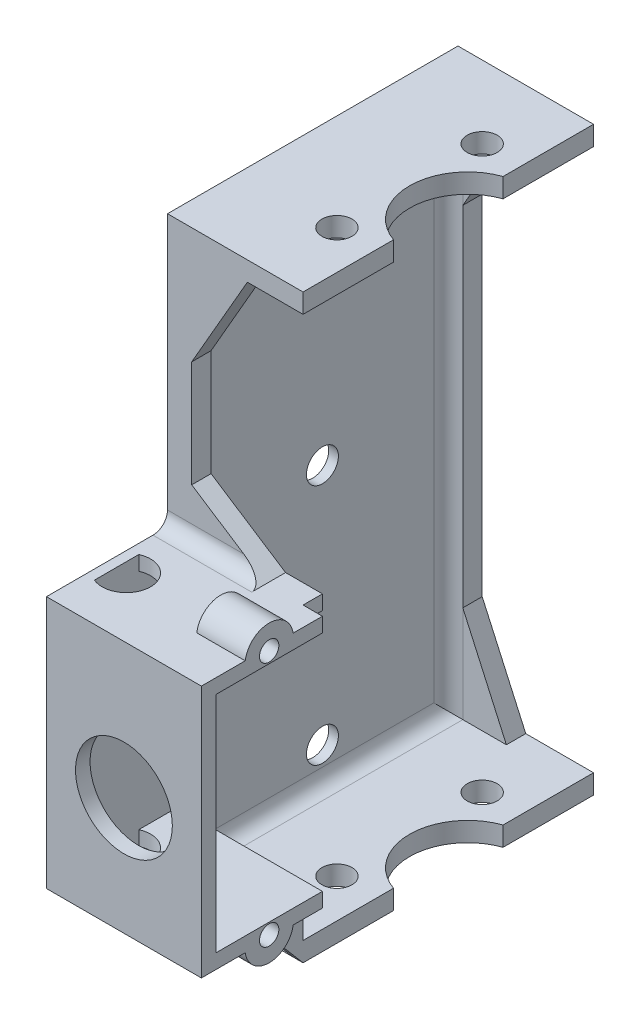
SolidWorks part; units mm, degrees
ref_plane "Alzado" through (0, 0, 0) normal (0, 0, 1) x (1, 0, 0)
ref_plane "Planta" through (0, 0, 0) normal (0, 1, 0) x (1, 0, 0)
ref_plane "Vista lateral" through (0, 0, 0) normal (1, 0, 0) x (0, 0, -1)
sketch "Croquis1" plane through (0, 0, 0) normal (1, 0, 0) x (0, 0, -1)
  line L0 (0, 12.5) -> (0, -12.5) construction
  line L1 (-15, 18) -> (15, 18) construction
  line L2 (-15, 18) -> (-15, -18)
  line L3 (-15, -18) -> (15, -18)
  line L4 (15, 18) -> (15, -18)
  line L5 (-15, 18) -> (15, -18) construction
  line L6 (-15, -18) -> (15, 18) construction
  line L9 (-15, 18) -> (-15, 42)
  line L10 (-15, 42) -> (15, 42)
  line L11 (15, 18) -> (15, 42)
  circle A0 centre (0, 12.5) radius 1.65
  circle A1 centre (0, -12.5) radius 1.65
  point P0 (0, 0)
  point P10 (0, 0)
  dimension "D3" = 25
  dimension "D4" = 3.3
  dimension "D1" = 30
  dimension "D2" = 36
  dimension "D5" = 24
extrude "Saliente-Extruir1" add sketch "Croquis1" along normal blind 1
sketch "screwHeadClearance" plane through (1, 0, 0) normal (1, 0, 0) x (0, 0, -1)
  circle A0 centre (0, 12.5) radius 3.175 construction
  circle A1 centre (0, -12.5) radius 3.175 construction
  point P6 (0, 0)
  point P7 (0, 0)
  dimension "D1" = 6.35
sketch "Croquis3" plane through (1, 0, 0) normal (1, 0, 0) x (0, 0, -1)
  line L0 (15, -18) -> (15, 42) construction
  line L1 (-15, 42) -> (15, 42)
  line L2 (-15, 42) -> (-15, 40)
  line L3 (-15, 40) -> (15, 40)
  line L4 (15, 42) -> (15, 40)
  line L6 (-15, -18) -> (15, -18)
  line L7 (-15, -18) -> (-15, -16)
  line L8 (-15, -16) -> (15, -16)
  line L9 (15, -18) -> (15, -16)
  point P12 (0, 0)
  dimension "D1" = 2
  dimension "D2" = 2
extrude "Saliente-Extruir2" add sketch "Croquis3" along normal blind 13
sketch "Croquis4" plane through (0, 42, 0) normal (0, 1, 0) x (1, 0, 0)
  line L0 (10, 7.5) -> (10, -7.5) construction
  line L1 (14, 15) -> (14, -15) construction
  line L2 (14, 5.6569) -> (14, -5.6569)
  circle A0 centre (10, 7.5) radius 1.55
  circle A1 centre (10, -7.5) radius 1.55
  arc A2 (14, -5.6569) -> (14, 5.6569) centre (16, 0) cw
  point P4 (10, 0)
  dimension "D2" = 3.1
  dimension "D4" = 6
  dimension "D1" = 15
  dimension "D3" = 4
  dimension "D5" = 2
extrude "Cortar-Extruir1" cut sketch "Croquis4" against normal through all
sketch "Croquis8" plane through (0, 0, 0) normal (1, 0, 0) x (0, 0, -1)
  line L0 (-15, 40) -> (-15, -16) construction
  line L1 (-26, 12.5) -> (-15, 12.5)
  line L2 (-26, 12.5) -> (-26, -10.608)
  line L3 (-26, -10.608) -> (-15, -10.608)
  line L4 (-15, 12.5) -> (-15, -10.608)
  point P6 (-20.5, 12.5)
  dimension "D1" = 11
  dimension "D2" = 23.108
extrude "Saliente-Extruir4" add sketch "Croquis8" along normal up to surface (1 mm away) up to face at (1, 12.5, -1.65)
sketch "Croquis9" plane through (0, 0, 0) normal (1, 0, 0) x (0, 0, -1)
  line L0 (-15, -10.608) -> (-15, -16) construction
  line L1 (-26, 12.5) -> (-15, 12.5)
  line L2 (-26, 12.5) -> (-26, -10.608)
  line L3 (-26, -10.608) -> (-15, -10.608)
  line L4 (-15, 12.5) -> (-15, -10.608)
  line L5 (-27.5, 14) -> (-15, 14)
  line L6 (-27.5, 14) -> (-27.5, -12.108)
  line L7 (-27.5, -12.108) -> (-15, -12.108)
  line L8 (-15, 14) -> (-15, -12.108)
  point P12 (-20.5, -10.608)
  dimension "D1" = 1.5
  dimension "D2" = 1.5
  dimension "D3" = 1.5
extrude "Saliente-Extruir5" add sketch "Croquis9" along normal blind 16 contours L8 L5 L6 L7 L3 L2 L1 region at (0, 0.946, 26.2895)
sketch "Croquis10" plane through (0, 14, 0) normal (0, 1, 0) x (1, 0, 0)
  line L0 (0, -27.5) -> (0, -15) construction
  line L1 (1, -18.9587) -> (1, -23.5413)
  circle A0 centre (2, -21.25) radius 2.5
  point P5 (0, -21.25)
  dimension "D2" = 5
  dimension "D1" = 2
  dimension "D3" = 1
extrude "Cortar-Extruir2" cut sketch "Croquis10" against normal through all contours L1 A0 region at (2.5463, 14, 21.25)
sketch "Croquis11" plane through (16, 0, 0) normal (1, 0, 0) x (0, 0, -1)
  line L0 (-26, 12.5) -> (-15, 12.5) construction
  line L1 (-20.5, 13.646) -> (-20.5, -11.754) construction
  line L2 (-26, 12.5) -> (-26, -10.608) construction
  line L3 (-22.7219, 12.5) -> (-18.2781, 12.5)
  line L4 (-15, 12.5) -> (-18.9587, 12.5) construction
  line L5 (-22.7219, -10.608) -> (-18.2781, -10.608)
  line L6 (-26, -10.608) -> (-15, -10.608) construction
  circle A0 centre (-20.5, 13.646) radius 1
  circle A1 centre (-20.5, 13.646) radius 2.5
  circle A2 centre (-20.5, -11.754) radius 1
  circle A3 centre (-20.5, -11.754) radius 2.5
  point P5 (-20.5, 12.5)
  point P8 (-20.5, 0.946)
  point P11 (-26, 0.946)
  line M2 (-15, 14) -> (-27.5, 14)
  line M4 (-27.5, -12.108) -> (-15, -12.108)
  dimension "D1" = 5
  dimension "D2" = 25.4
  dimension "D3" = 2
  dimension "D4" = 5
extrude "Saliente-Extruir6" add sketch "Croquis11" against normal blind 5 contours A3 A2 M4 | A1 A0 M2 region at (16, 14.9782, 20.5) region at (16, -13.0862, 20.5)
sketch "Croquis12" plane through (16, 0, 0) normal (1, 0, 0) x (0, 0, -1)
  circle A0 centre (-20.5, -11.754) radius 1
  circle A1 centre (-20.5, 13.646) radius 1
  arc A2 (-19.5648, 14) -> (-21.4352, 14) centre (-20.5, 13.646) ccw construction
  arc A3 (-21.4352, -12.108) -> (-19.5648, -12.108) centre (-20.5, -11.754) ccw construction
  point P10 (0, 0)
  point P12 (-20.5, -12.754)
extrude "Cortar-Extruir3" cut sketch "Croquis12" against normal blind 5
sketch "Croquis13" plane through (1, 0, 0) normal (1, 0, 0) x (0, 0, -1)
  line L0 (-5.6569, -16) -> (-15, -16) construction
  line L1 (-15, 40) -> (-13, 40)
  line L2 (-15, 40) -> (-15, -16)
  line L3 (-15, -16) -> (-13, -16)
  line L4 (-13, 40) -> (-13, -16)
  line L5 (-15, 40) -> (15, 40) construction
  line L6 (13, 40) -> (15, 40)
  line L7 (13, 40) -> (13, -16)
  line L8 (13, -16) -> (15, -16)
  line L9 (15, 40) -> (15, -16)
  dimension "D1" = 2
extrude "Saliente-Extruir7" add sketch "Croquis13" along normal blind 1.5
sketch "Croquis14" plane through (0, 0, 15) normal (0, 0, -1) x (-1, 0, 0)
  line L0 (-12.5, 12.5) -> (-2.5, 19)
  line L2 (-2.5, -16) -> (-2.5, 40) construction
  line L3 (-16, 12.5) -> (-1, 12.5) construction
  line L4 (-12.5, 12.5) -> (-2.5, 12.5)
  line L5 (-2.5, 12.5) -> (-2.5, 19)
  line L6 (-16, 12.5) -> (-2.5, 12.5) construction
  point P6 (-2.5, 12.5)
  dimension "D1" = 10
  dimension "D2" = 5
extrude "Saliente-Extruir8" add sketch "Croquis14" along normal blind 2
sketch "Croquis15" plane through (14, 0, 0) normal (1, 0, 0) x (0, 0, -1)
  line L0 (-13, 19) -> (-13, 12.5) construction
  line L5 (-15, 12.5) -> (-13, 12.5)
  line L6 (-15, 12.5) -> (-15, 14)
  line L7 (-15, 14) -> (-13, 14)
  line L8 (-13, 12.5) -> (-13, 14)
  line L9 (-18.0252, 14) -> (-15, 14) construction
extrude "Saliente-Extruir9" add sketch "Croquis15" against normal blind 5
sketch "Croquis16" plane through (0, 0, 0) normal (-1, 0, 0) x (0, 0, 1)
  line L0 (20, -12.108) -> (15, -18)
  line L1 (27.5, -12.108) -> (15, -12.108) construction
  line L2 (15, -12.108) -> (15, -18) construction
  dimension "D1" = 5
rib "Nervio4" sketch "Croquis16" sketch "Croquis16" thickness 1 extrusion direction parallel to sketch draft on no parameters "D1"=1
sketch "Croquis17" plane through (0, 0, 15) normal (0, 0, 1) x (1, 0, 0)
  line L0 (8.25, 40) -> (2.5, 30)
  line L1 (14, 40) -> (2.5, 40) construction
  line L2 (2.5, 40) -> (2.5, 19) construction
  dimension "D1" = 10
rib "Nervio5" sketch "Croquis17" sketch "Croquis17" thickness 2 extrusion direction parallel to sketch draft on no parameters "D1"=2
sketch "Croquis18" plane through (14, 0, 0) normal (1, 0, 0) x (0, 0, -1)
  line L0 (-15, -18) -> (-19.7445, -12.4091)
  line L1 (-20, -12.108) -> (-15, -18) construction
  line L2 (-19.5648, -12.108) -> (-15, -12.108)
  line L3 (-15, -12.108) -> (-15, -18)
  arc A1 (-19.7445, -12.4091) -> (-19.5648, -12.108) centre (-20.5, -11.754) ccw
  circle A4 centre (-20.5, -11.754) radius 1 construction
  point P5 (-19.3861, -12.8314)
  point P6 (0, 0)
  point P7 (0, 0)
  point P10 (-18.7694, -13.5582)
  point P11 (-18.6644, -13.0324)
  point P14 (-18.9049, -12.754)
  point P15 (-18.5581, -12.108)
  point P16 (-19.3074, -13.9512)
  dimension "D1" = 1
extrude "Saliente-Extruir10" add sketch "Croquis18" against normal blind 1
pattern_linear "MatrizL1" count 2 spacing 6 along (-1, 0, 0) of "Saliente-Extruir10"
sketch "Croquis19" plane through (0, 0, -15) normal (0, 0, -1) x (-1, 0, 0)
  line L0 (-8.25, 40) -> (-2.5, 30)
rib "Nervio9" sketch "Croquis19" sketch "Croquis19" thickness 2 extrusion direction parallel to sketch draft on no parameters "D1"=2
sketch "Croquis20" plane through (0, 0, -15) normal (0, 0, -1) x (-1, 0, 0)
  line L0 (-7, -16) -> (-2.5, -6)
  line L1 (-2.5, -16) -> (-2.5, 30) construction
  line L2 (-14, -16) -> (-2.5, -16) construction
  dimension "D1" = 10
rib "Nervio10" sketch "Croquis20" sketch "Croquis20" thickness 2 extrusion direction parallel to sketch draft on no parameters "D1"=2
fillet "Redondeo1" radius 1.5 5 edges at (5.0962, 14, 15) (1, 12, -13) (1, 12, 13) (1, -16, 0) (1, 40, 0)
sketch "Croquis21" plane through (0, 0, 27.5) normal (0, 0, 1) x (1, 0, 0)
  circle A0 centre (8, 0) radius 5
  point P2 (0, 0)
  point P4 (0, 0)
  dimension "D1" = 10
  dimension "D2" = 8
extrude "Cortar-Extruir4" cut sketch "Croquis21" against normal blind 2
